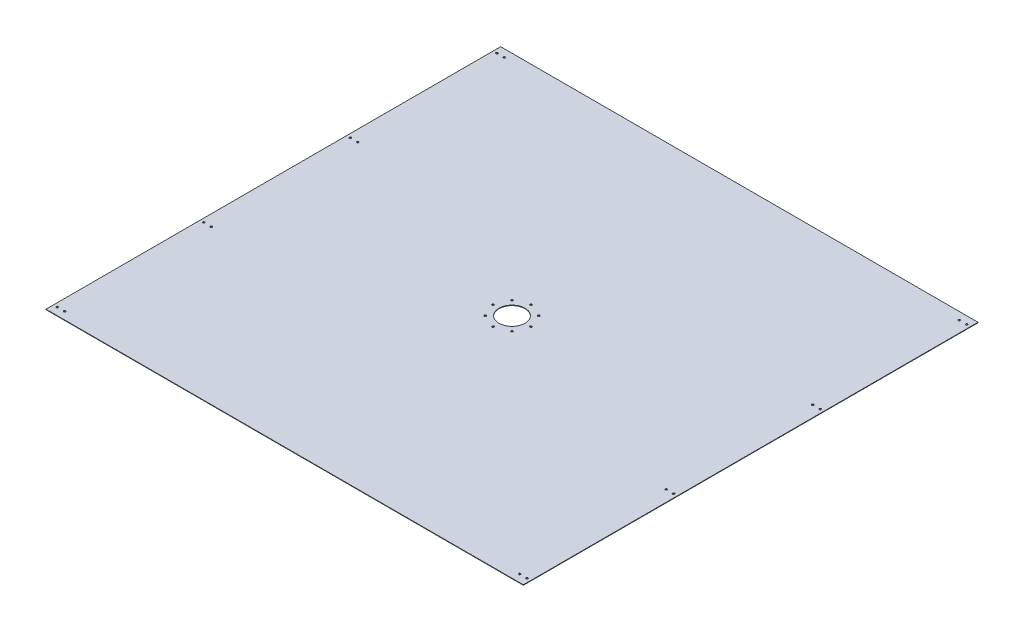
SolidWorks part; units mm, degrees
other "Markup1"
sketch "Sketch4" plane through (-640, 1.27, 609.6) normal (-0.1553, 0.9776, 0.1419) x (0.9864, 0.1457, 0.0762)
material "6061-T4 (SS)"
ref_plane "Front Plane" through (0, 0, 0) normal (0, 0, 1) x (1, 0, 0)
ref_plane "Top Plane" through (0, 0, 0) normal (0, 1, 0) x (1, 0, 0)
ref_plane "Right Plane" through (0, 0, 0) normal (1, 0, 0) x (0, 0, -1)
sketch "Sketch1" plane through (0, 0, 0) normal (0, 1, 0) x (1, 0, 0)
  line L1 (-657.225, -609.6) -> (657.225, -609.6)
  line L2 (-657.225, -609.6) -> (-657.225, 609.6)
  line L3 (-657.225, 609.6) -> (657.225, 609.6)
  line L4 (657.225, -609.6) -> (657.225, 609.6)
  line L5 (-657.225, -609.6) -> (657.225, 609.6) construction
  line L6 (-657.225, 609.6) -> (657.225, -609.6) construction
  point P0 (0, 0)
  dimension "D1" = 1219.2
  dimension "D2" = 1314.45
extrude "Boss-Extrude1" add sketch "Sketch1" along normal blind 1.27 contours L3 L4 L1 L2
sketch "Sketch2" plane through (0, 1.27, 0) normal (0, 1, 0) x (1, 0, 0)
  line L1 (-640, 609.6) -> (640, 609.6)
  line L2 (-640, 609.6) -> (-640, -609.6)
  line L3 (-640, -609.6) -> (640, -609.6)
  line L4 (640, 609.6) -> (640, -609.6)
  line L5 (-640, 609.6) -> (640, -609.6) construction
  line L6 (-640, -609.6) -> (640, 609.6) construction
  point P0 (0, 0)
  dimension "D1" = 1219.2
  dimension "D2" = 1280
extrude "Cut-Extrude1" cut sketch "Sketch2" against normal blind 2.54 flip side to cut
sketch "Sketch3" plane through (0, 1.27, 0) normal (0, 1, 0) x (1, 0, 0)
  line L0 (-640, 609.6) -> (-640, -609.6) construction
  line L1 (-640, -609.6) -> (640, -609.6) construction
  circle A0 centre (-630, -589.6) radius 2.65
  dimension "D1" = 5.3
  dimension "D2" = 10
  dimension "D3" = 20
extrude "Cut-Extrude2" cut sketch "Sketch3" against normal through all
pattern_linear "LPattern2" count 4 spacing 393.0227 along (0, 0, -1) count 2 spacing 20 along (1, 0, 0) of "Cut-Extrude2"
mirror "Mirror1" about plane through (0, 0, 0) normal (1, 0, 0) of "LPattern2"
sketch "Sketch5" plane through (0, 1.27, 0) normal (0, 1, 0) x (1, 0, 0)
  circle A0 centre (0, 0) radius 50.8
  circle A9 centre (0, 0) radius 34.925
  dimension "D1" = 101.6
  dimension "D6" = 69.85
extrude "Cut-Extrude4" cut sketch "Sketch5" against normal through all contours A9
sketch "Sketch10" plane through (0, 0, 0) normal (0, -1, 0) x (1, 0, 0)
  circle A0 centre (0, 0) radius 50.8
hole_wizard "Ø1.0mm Dowel Hole2" positions "Sketch11" profile "Sketch12" hole size "Ø1.0" standard "ANSI Metric" end condition through all
sketch "Sketch11" plane through (0, 0, 0) normal (0, -1, 0) x (-1, 0, 0)
  circle A0 centre (0, 0) radius 50.8 construction
  point P0 (0, 50.8)
sketch "Sketch12" plane through (0, 0, -50.8) normal (1, 0, 0) x (0, 0, -1)
  line L0 (0, 0) -> (0, 1.27)
  line L1 (0, 1.27) -> (2.65, 1.27)
  line L2 (2.65, 1.27) -> (2.65, 0)
  line L5 (2.65, 0) -> (0, 0)
  line L11 (0, -6.35) -> (0, 107.95) construction
  dimension "Thru Hole Dia." = 5.3
  dimension "Thru Hole Depth" = 1.27
ref_axis "Axis1" through (0, 1.3335, 0) along (0, -1, 0)
pattern_circular "CirPattern1" count 8 over 360 about axis through (0, 1.3335, 0) along (0, -1, 0) of "Ø1.0mm Dowel Hole2"
